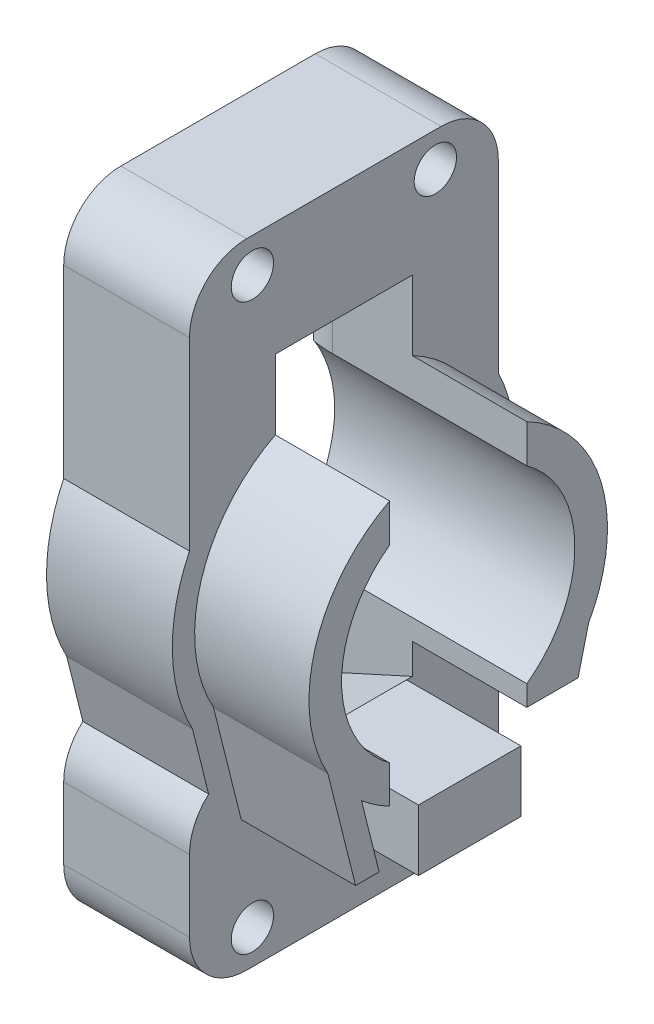
SolidWorks part; units mm, degrees
ref_plane "Alzado" through (0, 0, 0) normal (0, 0, 1) x (1, 0, 0)
ref_plane "Planta" through (0, 0, 0) normal (0, 1, 0) x (1, 0, 0)
ref_plane "Vista lateral" through (0, 0, 0) normal (1, 0, 0) x (0, 0, -1)
sketch "Croquis1" plane through (0, 0, 0) normal (1, 0, 0) x (0, 0, -1)
  line L0 (-15, 35) -> (-15, 30) construction
  line L1 (-5.7808, 0) -> (-24.2192, 0)
  line L5 (-15, 30) -> (-15, 10) construction
  line L6 (-25, 20) -> (-25, 0) construction
  line L7 (-5, 20) -> (-5, 0) construction
  line L8 (-28.2353, 12.9412) -> (-25.1894, 0.7575)
  line L9 (-1.7647, 12.9412) -> (-4.8106, 0.7575)
  circle A0 centre (-15, 20) radius 10
  arc A1 (-1.7647, 12.9412) -> (-28.2353, 12.9412) centre (-15, 20) ccw
  arc A2 (-24.2192, 0) -> (-25.1894, 0.7575) centre (-24.2192, 1) cw
  arc A3 (-5.7808, 0) -> (-4.8106, 0.7575) centre (-5.7808, 1) ccw
  dimension "D1" = 1
  dimension "D2" = 35
  dimension "D3" = 20
  dimension "D4" = 5
extrude "Saliente-Extruir1" add sketch "Croquis1" along normal blind 11
sketch "Croquis2" plane through (11, 0, 0) normal (1, 0, 0) x (0, 0, -1)
  line L9 (-23.4775, 1.95) -> (-6.5225, 1.95)
  line L10 (-6.5225, 1.95) -> (-3.5962, 13.6552)
  line L11 (-26.4038, 13.6552) -> (-23.4775, 1.95)
  line L12 (-23.4775, 1.95) -> (-6.5225, 1.95)
  line L13 (-6.5225, 1.95) -> (-3.5962, 13.6552)
  line L14 (-26.4038, 13.6552) -> (-23.4775, 1.95)
  circle A6 centre (-15, 20) radius 10 construction
  circle A7 centre (-15, 20) radius 10
  arc A9 (-3.5962, 13.6552) -> (-26.4038, 13.6552) centre (-15, 20) ccw
  arc A10 (-3.5962, 13.6552) -> (-26.4038, 13.6552) centre (-15, 20) ccw
  dimension "D1" = 1.95
extrude "Saliente-Extruir2" add sketch "Croquis2" along normal blind 10
sketch "Croquis3" plane through (21, 0, 0) normal (1, 0, 0) x (0, 0, -1)
  line L0 (-9.5225, 1.95) -> (-9.5225, 9.95)
  line L1 (-23.4775, 1.95) -> (-6.5225, 1.95) construction
  line L2 (-9.5225, 9.95) -> (-4.5225, 9.95)
  line L3 (-6.5225, 1.95) -> (-3.5962, 13.6552) construction
  line L4 (-9.5225, 1.95) -> (-6.5225, 1.95)
  line L5 (-6.5225, 1.95) -> (-4.5225, 9.95)
  line L6 (-21.7673, 1.95) -> (-21.7673, 3.95) construction
  line L7 (-23.4775, 1.95) -> (-18.4775, 1.95)
  line L8 (-23.4775, 1.95) -> (-23.9775, 3.95)
  line L9 (-21.7673, 3.95) -> (-21.9159, 3.95) construction
  line L10 (-24.4635, 14.1403) -> (-21.5372, 2.4351)
  line L11 (-23.2421, 9.2546) -> (-21.9159, 3.95)
  line L12 (-21.9159, 3.95) -> (-23.9775, 3.95)
  line L13 (-26.4038, 13.6552) -> (-23.4775, 1.95) construction
  line L14 (-18.4775, 1.95) -> (-18.4775, 6.9452)
  line L15 (-23.2421, 9.2546) -> (-23.461, 10.1303)
  line L16 (-18.4775, 6.9452) -> (-18.4775, 7.4737)
  circle A6 centre (-15, 20) radius 13
  arc A7 (-23.461, 10.1303) -> (-18.4775, 7.4737) centre (-15, 20) ccw
  dimension "D2" = 8
  dimension "D3" = 5
  dimension "D4" = 2
  dimension "D6" = 5
  dimension "D5" = 2
  dimension "D7" = 3
extrude "Cortar-Extruir3" cut sketch "Croquis3" against normal blind 10
sketch "Croquis8" plane through (0, 1.95, 0) normal (0, -1, 0) x (1, 0, 0)
  line L1 (11, 14) -> (13.2177, 14) construction
  line L2 (11, 18.4775) -> (11, 9.5225) construction
  line L4 (14.45, 14) -> (16, 14) construction
  line L5 (16, 14) -> (17.55, 14) construction
  line L7 (17.55, 14) -> (21, 14) construction
  line L8 (21, 18.4775) -> (21, 9.5225) construction
  circle A0 centre (16, 14) radius 1.55
  dimension "D2" = 3.1
extrude "Cortar-Extruir4" cut sketch "Croquis8" against normal blind 5
sketch "Croquis10" plane through (0, 0, 0) normal (-1, 0, 0) x (0, 0, 1)
  line L4 (15, 32.3) -> (20.5, 32.3)
  line L5 (2.7, 20) -> (5, 20)
  line L6 (2.7, 20) -> (2.7, 25.5)
  line L9 (2.7, 20) -> (2.7, 14.5)
  line L10 (15, 32.3) -> (9.5, 32.3)
  line L11 (2.7, 25.5) -> (6.3506, 25.5)
  line L12 (2.7, 14.5) -> (6.3506, 14.5)
  line L13 (20.5, 32.3) -> (20.5, 28.6494)
  line L14 (9.5, 32.3) -> (9.5, 28.6494)
  line L16 (27.3, 20) -> (27.3, 14.5)
  line L17 (27.3, 20) -> (27.3, 25.5)
  line L18 (27.3, 14.5) -> (23.6494, 14.5)
  line L19 (27.3, 25.5) -> (23.6494, 25.5)
  line L21 (15, 20) -> (15, 30.25) construction
  arc A1 (9.5, 28.6494) -> (6.3506, 25.5) centre (15, 20) ccw
  arc A2 (23.6494, 25.5) -> (20.5, 28.6494) centre (15, 20) ccw
  arc A3 (6.3506, 14.5) -> (23.6494, 14.5) centre (15, 20) ccw
  circle A4 centre (15, 20) radius 10 construction
  dimension "D1" = 20.5
  dimension "D2" = 2.3
  dimension "D3" = 5.5
  dimension "D4" = 5.5
  dimension "D5" = 3
sketch "Croquis11" plane through (0, 0, 0) normal (-1, 0, 0) x (0, 0, 1)
  line L0 (15, 30.2) -> (15, 32.7) construction
  line L1 (21, 32.7) -> (9, 32.7)
  line L2 (9, 32.7) -> (9, 28.2486)
  line L3 (15, 20) -> (9.5566, 20) construction
  line L4 (21, 32.7) -> (21, 28.2486)
  line L5 (21, 7.3) -> (21, 11.7514)
  line L6 (21, 7.3) -> (9, 7.3)
  line L7 (9, 7.3) -> (9, 11.7514)
  arc A2 (21, 11.7514) -> (21, 28.2486) centre (15, 20) ccw
  arc A3 (9, 28.2486) -> (9, 11.7514) centre (15, 20) ccw
  dimension "D2" = 2.5
  dimension "D3" = 6
extrude "Cortar-Extruir5" cut sketch "Croquis11" against normal up to surface (21 mm away) up to face at (21, 9.5735, 16.0023)
sketch "Croquis12" plane through (21, 0, 0) normal (1, 0, 0) x (0, 0, -1)
  line L1 (-18.0021, 32.7) -> (-11.9979, 32.7)
  line L2 (-18.0021, 32.7) -> (-11.9979, 32.7)
  arc A1 (-11.9979, 32.7) -> (-18.0021, 32.7) centre (-15, 20) ccw
  arc A2 (-11.9979, 32.7) -> (-18.0021, 32.7) centre (-15, 20) ccw
  dimension "D1" = 0
extrude "Cortar-Extruir6" cut sketch "Croquis12" against normal blind 10
sketch "Croquis18" plane through (0, 0, 0) normal (-1, 0, 0) x (0, 0, 1)
  line L1 (1.5, 7.3) -> (3.175, 7.3)
  line L2 (1.5, 7.3) -> (1.5, -7.7)
  line L3 (1.5, -7.7) -> (28.5, -7.7)
  line L4 (28.5, 7.3) -> (28.5, -7.7)
  line L5 (9, 11.7514) -> (9, 28.2486) construction
  line L6 (1.5, 47.7) -> (28.5, 47.7)
  line L7 (15, 20) -> (9, 20) construction
  line L8 (28.5, 32.7) -> (28.5, 47.7)
  line L9 (1.5, 32.7) -> (7.0181, 32.7)
  line L10 (1.5, 32.7) -> (1.5, 47.7)
  line L11 (26.825, 7.3) -> (28.5, 7.3)
  line L12 (22.9819, 32.7) -> (28.5, 32.7)
  line L14 (25.1894, 0.7575) -> (28.2353, 12.9412)
  line L15 (1.7647, 12.9412) -> (4.8106, 0.7575)
  line L16 (5.7808, 0) -> (24.2192, 0)
  line L17 (25.1894, 0.7575) -> (26.825, 7.3)
  line L18 (3.175, 7.3) -> (4.8106, 0.7575)
  line L19 (5.7808, 0) -> (24.2192, 0)
  arc A3 (24.2192, 0) -> (25.1894, 0.7575) centre (24.2192, 1) ccw
  arc A4 (28.2353, 12.9412) -> (1.7647, 12.9412) centre (15, 20) ccw
  arc A5 (4.8106, 0.7575) -> (5.7808, 0) centre (5.7808, 1) ccw
  arc A6 (24.2192, 0) -> (25.1894, 0.7575) centre (24.2192, 1) ccw
  arc A7 (22.9819, 32.7) -> (7.0181, 32.7) centre (15, 20) ccw
  arc A8 (4.8106, 0.7575) -> (5.7808, 0) centre (5.7808, 1) ccw
  dimension "D1" = 27
  dimension "D2" = 15
  dimension "D3" = 0
extrude "Saliente-Extruir5" add sketch "Croquis18" against normal up to surface (11 mm away) up to face at (11, 8.187, 15)
sketch "Croquis19" plane through (11, 0, 0) normal (1, 0, 0) x (0, 0, -1)
  line L0 (-28.5, 7.3) -> (-36.6214, 7.3) construction
  line L1 (-36.6214, 7.3) -> (-36.6214, 32.7) construction
  line L2 (-15, -7.7) -> (-15, -4.7) construction
  line L3 (-28.5, -7.7) -> (-1.5, -7.7) construction
  line L4 (-36.6214, 20) -> (-32.4655, 20) construction
  line L5 (-28.5, 32.7) -> (-36.6214, 32.7) construction
  line L6 (-15, -4.7) -> (-23, -4.7) construction
  circle A0 centre (-23, -4.7) radius 1.85
  circle A1 centre (-7, -4.7) radius 1.85
  circle A2 centre (-7, 44.7) radius 1.85
  circle A3 centre (-23, 44.7) radius 1.85
  dimension "D1" = 3.7
  dimension "D2" = 8
  dimension "D3" = 3
extrude "Cortar-Extruir9" cut sketch "Croquis19" against normal up to next
sketch "Croquis21" plane through (0, 0, 0) normal (-1, 0, 0) x (0, 0, 1)
  line L0 (22.9819, 32.7) -> (28.5, 32.7) construction
  line L1 (1.5, 32.7) -> (7.0181, 32.7) construction
  line L2 (22.9819, 32.7) -> (28.5, 32.7)
  line L3 (1.5, 32.7) -> (7.0181, 32.7)
  line L4 (1.5, 32.7) -> (1.5, 26.5383)
  line L5 (28.5, 32.7) -> (28.5, 26.5383)
  arc A0 (28.2353, 12.9412) -> (22.9819, 32.7) centre (15, 20) ccw construction
  arc A1 (7.0181, 32.7) -> (1.7647, 12.9412) centre (15, 20) ccw construction
  arc A2 (28.5, 26.5383) -> (22.9819, 32.7) centre (15, 20) ccw
  arc A3 (7.0181, 32.7) -> (1.5, 26.5383) centre (15, 20) ccw
extrude "Saliente-Extruir7" add sketch "Croquis21" against normal up to surface (11 mm away) up to face at (11, 44.7, 24.85)
sketch "Croquis22" plane through (0, 0, 9) normal (0, 0, 1) x (1, 0, 0)
  line L0 (0, 7.3) -> (0, 2.3)
  line L1 (0, 2.3) -> (11, 7.3)
  line L2 (11, 7.3) -> (0, 7.3)
  line L4 (0, 32.7) -> (11, 32.7)
  line L5 (0, 32.7) -> (0, 37.7)
  line L6 (0, 37.7) -> (11, 37.7)
  line L7 (11, 32.7) -> (11, 37.7)
  dimension "D1" = 5
  dimension "D2" = 5
extrude "Cortar-Extruir10" cut sketch "Croquis22" along normal blind 12
sketch "Croquis23" plane through (0, 0, 9) normal (0, 0, 1) x (1, 0, 0)
  line L0 (0, 37.7) -> (11, 37.7)
  line L1 (0, 37.7) -> (0, 41.7)
  line L2 (0, 41.7) -> (11, 37.7)
  dimension "D1" = 4
extrude "Cortar-Extruir11" cut sketch "Croquis23" along normal up to surface (12 mm away) up to face at (10.6667, 32.5125, 21)
fillet "Redondeo1" radius 4 4 edges at (0, 34.9743, 21) (0, 34.9743, 9) (0, 7.0257, 9) (0, 7.0257, 21)
fillet "Redondeo2" radius 5 2 edges at (5.5, 7.3, 28.5) (5.5, 7.3, 1.5)
fillet "Redondeo3" radius 5 4 edges at (5.5, 47.7, 1.5) (5.5, 47.7, 28.5) (5.5, -7.7, 28.5) (5.5, -7.7, 1.5)
